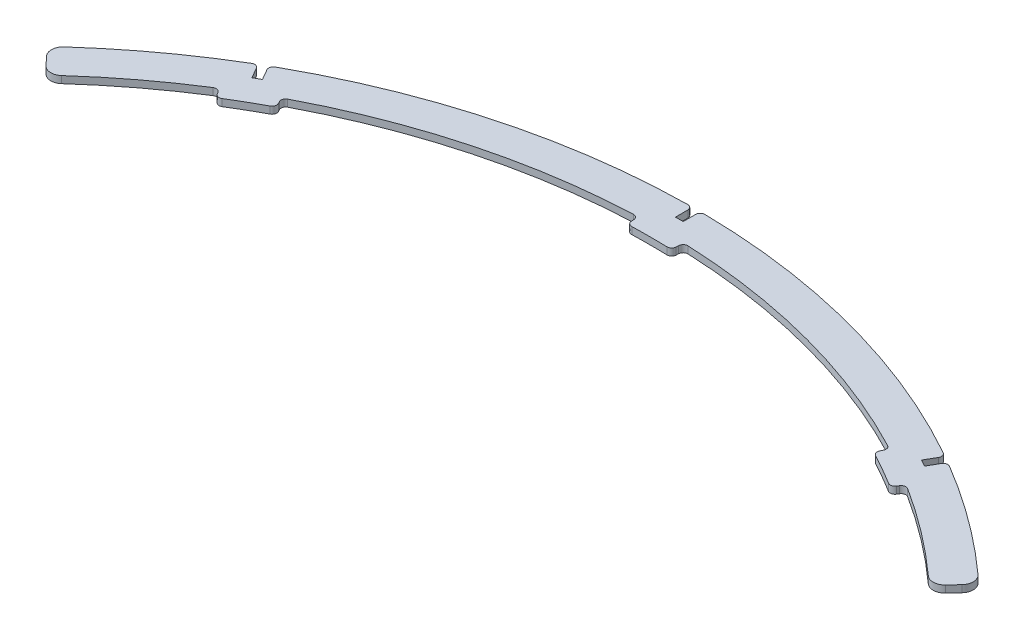
SolidWorks part; units mm, degrees
ref_plane "Front Plane" through (0, 0, 0) normal (0, 0, 1) x (1, 0, 0)
ref_plane "Top Plane" through (0, 0, 0) normal (0, 1, 0) x (1, 0, 0)
ref_plane "Right Plane" through (0, 0, 0) normal (1, 0, 0) x (0, 0, -1)
sketch "Sketch1" plane through (0, 0, 0) normal (0, 1, 0) x (1, 0, 0)
  line L0 (0, 0) -> (0, 291.5) construction
  line L1 (-145.75, 252.4464) -> (0, 0) construction
  line L2 (0, 0) -> (145.75, 252.4464) construction
  line L3 (-147.1766, 251.6174) -> (-143.5289, 245.2994)
  line L4 (-143.5289, 245.2994) -> (-140.6711, 246.9494)
  line L5 (-140.6711, 246.9494) -> (-144.3187, 253.2674)
  line L6 (-1.65, 291.4953) -> (-1.65, 284.2)
  line L7 (1.65, 284.2) -> (1.65, 291.4953)
  line L8 (-1.65, 284.2) -> (1.65, 284.2)
  line L9 (144.3187, 253.2674) -> (140.6711, 246.9494)
  line L10 (143.5289, 245.2994) -> (147.1766, 251.6174)
  line L11 (140.6711, 246.9494) -> (143.5289, 245.2994)
  line L12 (-154.4715, 247.206) -> (-143.8731, 230.2451)
  line L13 (-127.4615, 239.7203) -> (-129.8089, 244.135)
  line L14 (154.4715, 247.206) -> (143.8731, 230.2451)
  line L15 (127.4615, 239.7203) -> (129.8089, 244.135)
  line L16 (9.4752, 271.3346) -> (9.6497, 276.3316)
  line L17 (-9.6497, 276.3316) -> (-9.4752, 271.3346)
  circle A0 centre (0, 0) radius 291.5 construction
  circle A1 centre (0, 0) radius 284.5 construction
  arc A2 (1.65, 291.4953) -> (144.3187, 253.2674) centre (0, 0) cw
  arc A3 (-144.3187, 253.2674) -> (-1.65, 291.4953) centre (0, 0) cw
  arc A4 (-129.8089, 244.135) -> (-9.6497, 276.3316) centre (0, 0) cw
  arc A5 (-147.1766, 251.6174) -> (-154.4715, 247.206) centre (0, 0) ccw
  arc A6 (147.1766, 251.6174) -> (154.4715, 247.206) centre (0, 0) cw
  arc A7 (-143.8731, 230.2451) -> (-127.4615, 239.7203) centre (0, 0) cw
  arc A8 (143.8731, 230.2451) -> (127.4615, 239.7203) centre (0, 0) ccw
  arc A9 (-9.4752, 271.3346) -> (9.4752, 271.3346) centre (0, 0) cw
  arc A10 (9.6497, 276.3316) -> (129.8089, 244.135) centre (0, 0) cw
  point P12 (-142.25, 246.3842)
  point P23 (0, 0)
  point P41 (0, 0)
  dimension "D1" = 583
  dimension "D2" = 569
  dimension "D3" = 30
  dimension "D4" = 30
  dimension "D5" = 0.3
  dimension "D6" = 1.65
  dimension "D7" = 1.65
  dimension "D9" = 15
  dimension "D10" = 2
  dimension "D11" = 20
  dimension "D12" = 2
  dimension "D8" = 3
  dimension "D13" = 2
extrude "Boss-Extrude1" add sketch "Sketch1" along normal blind 3
fillet "Fillet1" radius 2 8 edges at (127.4615, 1.5, -239.7203) (129.8089, 1.5, -244.135) (-127.4615, 1.5, -239.7203) (-129.8089, 1.5, -244.135) (-9.6497, 1.5, -276.3316) (-9.4752, 1.5, -271.3346) (9.4752, 1.5, -271.3346) (9.6497, 1.5, -276.3316)
fillet "Fillet2" radius 2 4 edges at (-154.4715, 1.5, -247.206) (-143.8731, 1.5, -230.2451) (154.4715, 1.5, -247.206) (143.8731, 1.5, -230.2451)
fillet "Fillet3" radius 2 6 edges at (147.1766, 1.5, -251.6174) (144.3187, 1.5, -253.2674) (-1.65, 1.5, -291.4953) (1.65, 1.5, -291.4953) (-144.3187, 1.5, -253.2674) (-147.1766, 1.5, -251.6174)
sketch "Sketch2" plane through (0, 3, 0) normal (0, 1, 0) x (1, 0, 0)
  line L0 (-152.76, 248.2673) -> (-146.5227, 234.4853)
  line L1 (-191.9523, 205.8436) -> (-195.3628, 209.5009)
  line L2 (-145.75, 252.4464) -> (0, 0) construction
  line L3 (-153.408, 245.5041) -> (-144.929, 231.935) construction
  line L4 (0, -1000) -> (0, 49000) construction
  line L5 (191.9523, 205.8436) -> (195.3628, 209.5009)
  line L6 (152.76, 248.2673) -> (146.5227, 234.4853)
  arc A0 (-152.76, 248.2673) -> (-195.0517, 216.6266) centre (0, 0) ccw
  circle A1 centre (0, 0) radius 291.5 construction
  arc A2 (-146.5227, 234.4853) -> (-184.951, 205.5368) centre (0, 0) ccw
  arc A3 (-9.6497, 276.3316) -> (-129.8089, 244.135) centre (0, 0) ccw construction
  arc A5 (-195.0517, 216.6266) -> (-195.3628, 209.5009) centre (-191.706, 212.9109) ccw
  arc A6 (-184.951, 205.5368) -> (-191.9523, 205.8436) centre (-188.2955, 209.2536) cw
  arc A7 (184.951, 205.5368) -> (191.9523, 205.8436) centre (188.2955, 209.2536) ccw
  arc A8 (195.0517, 216.6266) -> (195.3628, 209.5009) centre (191.706, 212.9109) cw
  arc A9 (146.5227, 234.4853) -> (184.951, 205.5368) centre (0, 0) cw
  arc A10 (152.76, 248.2673) -> (195.0517, 216.6266) centre (0, 0) cw
  dimension "D2" = 5
  dimension "D1" = 13
extrude "Boss-Extrude2" add sketch "Sketch2" against normal up to surface (3 mm away) up to face at (0, 0, -257.126)
fillet "Fillet4" radius 2 2 edges at (-146.5227, 1.5, -234.4853) (146.5227, 1.5, -234.4853)
equation "\"D4@Sketch1\"=\"D3@Sketch1\""
equation "\"D7@Sketch1\"=\"D6@Sketch1\""
